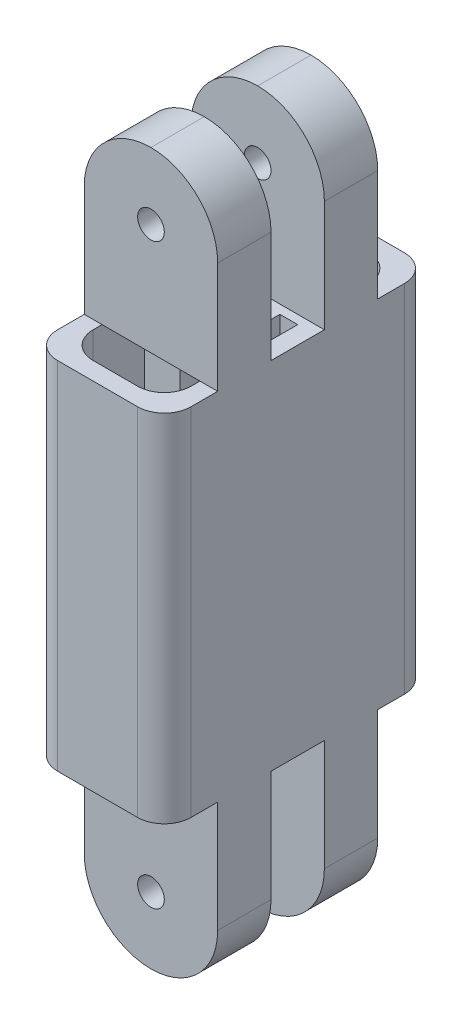
SolidWorks part; units mm, degrees
ref_plane "Front Plane" through (0, 0, 0) normal (0, 0, 1) x (1, 0, 0)
ref_plane "Top Plane" through (0, 0, 0) normal (0, 1, 0) x (1, 0, 0)
ref_plane "Right Plane" through (0, 0, 0) normal (1, 0, 0) x (0, 0, -1)
sketch "Sketch1" plane through (0, 0, 0) normal (0, 1, 0) x (1, 0, 0)
  line L0 (0, 0) -> (-10.7454, 0) construction
  line L1 (-7.5, -15) -> (7.5, -15)
  line L2 (-7.5, -15) -> (-7.5, 15)
  line L3 (-7.5, 15) -> (7.5, 15)
  line L4 (7.5, -15) -> (7.5, 15)
  line L5 (-7.5, -15) -> (7.5, 15) construction
  line L6 (-7.5, 15) -> (7.5, -15) construction
  line L7 (-5.5, -13) -> (5.5, -13)
  line L8 (-5.5, -13) -> (-5.5, -4.2085)
  line L9 (-5.5, 13) -> (5.5, 13)
  line L10 (5.5, -13) -> (5.5, -4)
  line L11 (-5.5, -13) -> (5.5, 13) construction
  line L12 (-5.5, 13) -> (5.5, -13) construction
  line L13 (-10.7454, 0) -> (11.7241, 0) construction
  line L14 (-5.5, 4.1445) -> (-1.5, 4.1445)
  line L15 (-1.5, 4.1445) -> (-1.5, -4.2085)
  line L16 (-1.5, -4.2085) -> (-5.5, -4.2085)
  line L17 (-5.5, 2) -> (-3.5, 2)
  line L18 (-3.5, 2) -> (-3.5, -2.4963)
  line L19 (-3.5, -2.4963) -> (-5.5, -2.4963)
  line L20 (5.5, 4.1445) -> (1.5, 4.1445)
  line L21 (1.5, 4.1445) -> (1.5, -4)
  line L22 (1.5, -4) -> (5.5, -4)
  line L23 (5.5, 2) -> (3.5, 2)
  line L24 (3.5, 2) -> (3.5, -2)
  line L25 (3.5, -2) -> (5.5, -2)
  line L26 (-5.5, 4.1445) -> (-5.5, 13)
  line L27 (5.5, 4.1445) -> (5.5, 13)
  line L28 (-5.5, 2) -> (-5.5, -2.4963)
  line L29 (5.5, 2) -> (5.5, -2)
  point P0 (0, 0)
  point P6 (0, 0)
  dimension "D1" = 2
  dimension "D2" = 2
  dimension "D3" = 2
  dimension "D4" = 2
  dimension "D5" = 2
  dimension "D6" = 2
  dimension "D7" = 2
  dimension "D8" = 2
  dimension "D9" = 2
  dimension "D10" = 2
  dimension "D11" = 15
  dimension "D12" = 30
extrude "Boss-Extrude1" add sketch "Sketch1" along normal blind 40 from offset 20 offset against normal yes
sketch "Sketch2" plane through (0, -20, 0) normal (0, -1, 0) x (1, 0, 0)
  line L0 (-7.5, -15) -> (-7.5, 15) construction
  line L3 (7.5, 9) -> (-7.5, 9)
  line L8 (7.5, -9) -> (-7.5, -9)
  line L11 (-7.5, -9) -> (-7.5, -3)
  line L12 (-7.5, -3) -> (7.5, -3)
  line L13 (7.5, 15) -> (7.5, -15) construction
  line L14 (7.5, -3) -> (7.5, -9)
  line L15 (-7.5, 9) -> (-7.5, 3)
  line L16 (-7.5, 3) -> (7.5, 3)
  line L17 (7.5, 3) -> (7.5, 9)
  line L18 (-7.5, 15) -> (7.5, 15) construction
  line L19 (7.5, -15) -> (-7.5, -15) construction
  dimension "D1" = 6
  dimension "D2" = 6
  dimension "D3" = 6
  dimension "D4" = 6
extrude "Boss-Extrude2" add sketch "Sketch2" along normal blind 20
fillet "Fillet1" radius 7.5 4 edges at (7.5, -40, 6) (7.5, -40, -6) (-7.5, -40, 6) (-7.5, -40, -6)
sketch "Sketch3" plane through (0, 0, 9) normal (0, 0, 1) x (1, 0, 0)
  circle A1 centre (0, -32.5) radius 1.5
  dimension "D1" = 3
extrude "Cut-Extrude1" cut sketch "Sketch3" against normal through all
mirror "Mirror1" about plane through (0, 0, 0) normal (0, 1, 0) of "Boss-Extrude2", "Cut-Extrude1", "Fillet1"
fillet "Fillet2" radius 3 8 edges at (-5.5, 0, 13) (5.5, 0, 13) (5.5, 0, -13) (-5.5, 0, -13) (-7.5, 0, -15) (-7.5, 0, 15) (7.5, 0, 15) (7.5, 0, -15)
